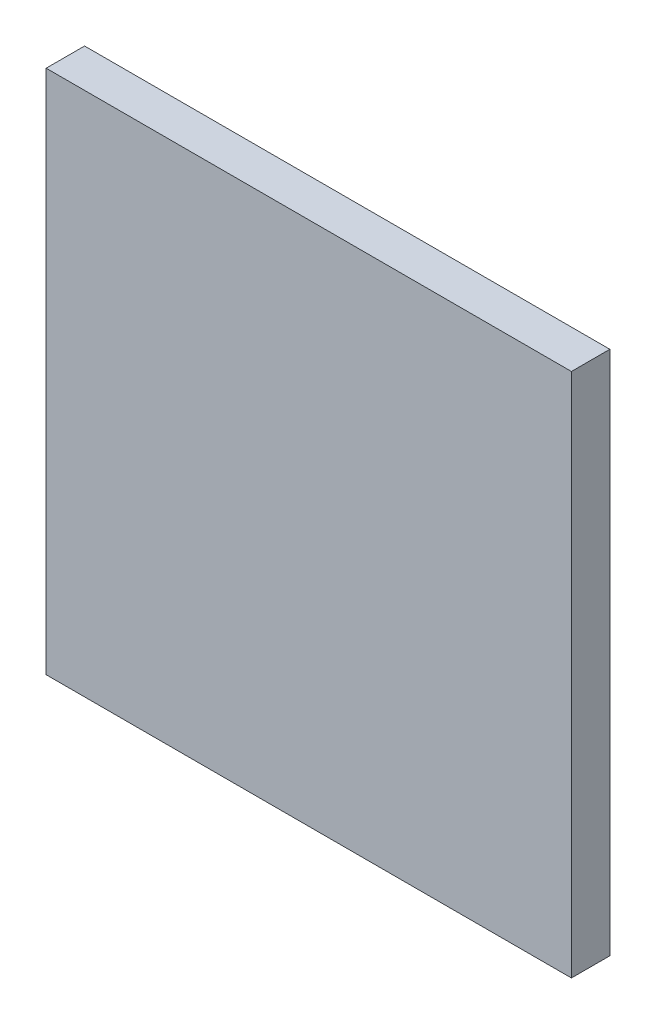
SolidWorks part; units mm, degrees
ref_plane "前视基准面" through (0, 0, 0) normal (0, 0, 1) x (1, 0, 0)
ref_plane "上视基准面" through (0, 0, 0) normal (0, 1, 0) x (1, 0, 0)
ref_plane "右视基准面" through (0, 0, 0) normal (1, 0, 0) x (0, 0, -1)
sketch "草图1" plane through (0, 0, 0) normal (0, 0, 1) x (1, 0, 0)
  line L1 (-152.7457, 91.3447) -> (7.2543, 91.3447)
  line L2 (-152.7457, 91.3447) -> (-152.7457, -68.6553)
  line L3 (-152.7457, -68.6553) -> (7.2543, -68.6553)
  line L4 (7.2543, 91.3447) -> (7.2543, -68.6553)
  dimension "D1" = 160
  dimension "D2" = 160
sketch "草图2" plane through (0, 0, 0) normal (0, 0, 1) x (1, 0, 0)
  line L0 (-152.7457, 91.3447) -> (7.2543, 91.3447) construction
  line L1 (-154.7457, 93.3447) -> (9.2543, 93.3447)
  line L2 (-154.7457, 93.3447) -> (-154.7457, -70.6553)
  line L3 (-154.7457, -70.6553) -> (9.2543, -70.6553)
  line L4 (9.2543, 93.3447) -> (9.2543, -70.6553)
  line L5 (-152.7457, 91.3447) -> (-152.7457, -68.6553) construction
  line L6 (7.2543, 91.3447) -> (7.2543, -68.6553) construction
  line L7 (-152.7457, -68.6553) -> (7.2543, -68.6553) construction
  dimension "D1" = 2
  dimension "D2" = 2
  dimension "D3" = 2
  dimension "D4" = 2
extrude "凸台-拉伸1" add sketch "草图2" along normal blind 12
extrude "凸台-拉伸2" add sketch "草图1" along normal blind 10 separate body
combine bodies "组合1" operation type subtract main body 101 bodies to subtract 102
